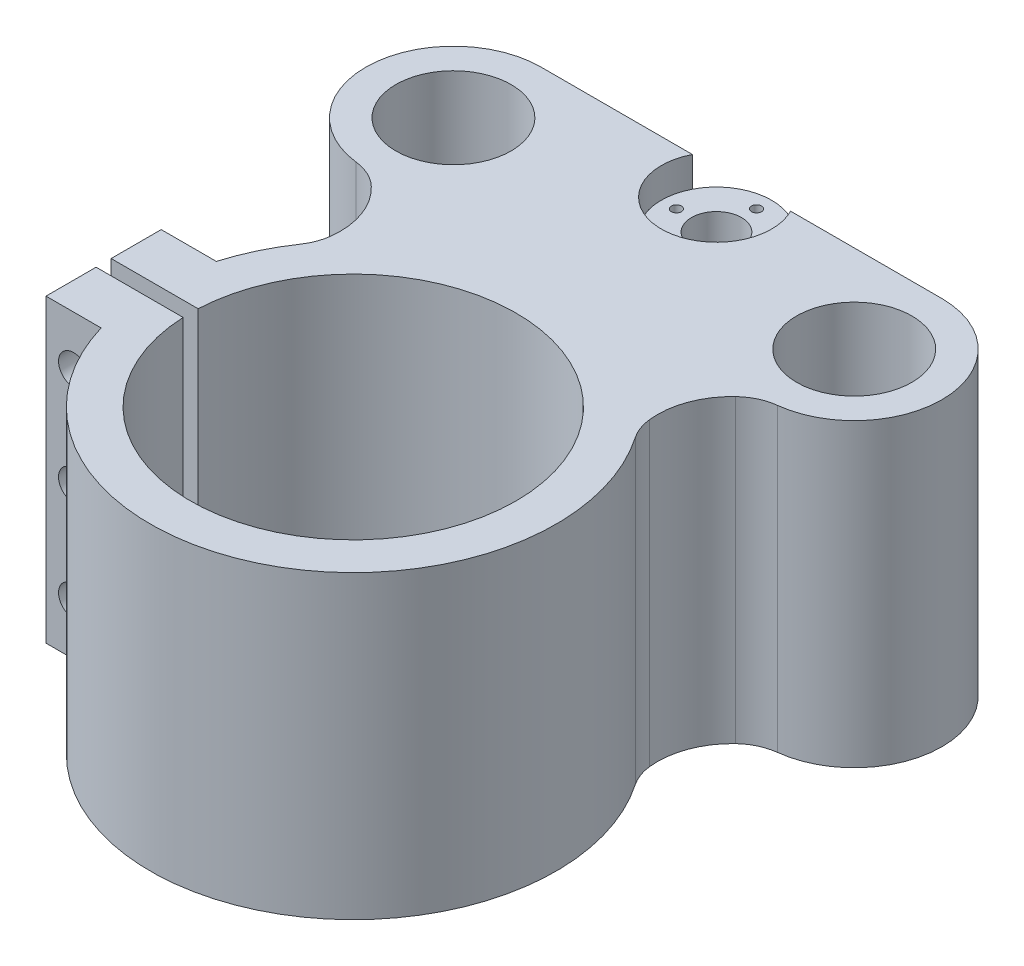
SolidWorks part; units mm, degrees
ref_plane "Front Plane" through (0, 0, 0) normal (0, 0, 1) x (1, 0, 0)
ref_plane "Top Plane" through (0, 0, 0) normal (0, 1, 0) x (1, 0, 0)
ref_plane "Right Plane" through (0, 0, 0) normal (1, 0, 0) x (0, 0, -1)
sketch "Sketch1" plane through (0, 0, 0) normal (0, 1, 0) x (1, 0, 0)
  line L0 (27.0908, 104.5706) -> (107.0908, 104.5706) construction
  line L3 (67.0908, 44.5706) -> (8.9284, 44.5706) construction
  line L5 (67.0908, 44.5706) -> (94.3328, 44.5706) construction
  line L6 (17.2579, 46.0706) -> (34.6255, 46.0706)
  line L7 (17.2579, 56.0706) -> (28.2579, 56.0706)
  line L8 (67.0908, 104.5706) -> (67.0908, 153.14) construction
  line L9 (67.0908, 111.1474) -> (67.0908, 30.162) construction
  line L10 (17.2579, 46.0706) -> (17.2579, 56.0706)
  line L11 (17.2579, 43.0706) -> (34.6255, 43.0706)
  line L12 (17.2579, 43.0706) -> (17.2579, 33.0706)
  line L14 (17.2579, 33.0706) -> (28.2579, 33.0706)
  line L15 (27.0908, 122.0706) -> (107.0908, 122.0706)
  circle A0 centre (27.0908, 104.5706) radius 11.5
  circle A2 centre (27.0908, 104.5706) radius 17.5
  arc A5 (34.6255, 43.0706) -> (34.6255, 46.0706) centre (67.0908, 44.5706) ccw
  arc A6 (28.2579, 33.0706) -> (28.2579, 56.0706) centre (67.0908, 44.5706) ccw
  circle A9 centre (67.0908, 44.5706) radius 32.5 construction
  circle A10 centre (67.0908, 44.5706) radius 40.5 construction
  arc A15 (27.0908, 87.0706) -> (34.6255, 68.7832) centre (20.4303, 73.6304) cw
  arc A16 (107.0908, 87.0706) -> (99.5562, 68.7832) centre (113.7514, 73.6304) ccw
  circle A17 centre (107.0908, 104.5706) radius 11.5
  circle A18 centre (107.0908, 104.5706) radius 17.5
  point P25 (67.0908, 122.0706)
  dimension "D1" = 23
  dimension "D4" = 60
  dimension "D7" = 65
  dimension "D8" = 8
  dimension "D13" = 11
  dimension "D5" = 15
  dimension "D2" = 80
  dimension "D9" = 0
  dimension "D11" = 1.5
  dimension "D12" = 10
  dimension "D3" = 6
extrude "Boss-Extrude1" add sketch "Sketch1" along normal blind 60 contours A6 A5 | A2 A0 | A6 A2 | A2 A6 | A6 | A6 L10 | A6 | A18 A17 region at (18.4712, 0, -51.0706) region at (67.0908, 0, -99.9598) region at (10.0858, 0, -104.5706) region at (90.0858, 0, -104.5706)
sketch "Sketch2" plane through (-1.1118, 0, -33.0706) normal (0, 0, 1) x (1, 0, 0)
  line L0 (30.4702, 30) -> (39.2061, 30) construction
  line L1 (18.3696, 60) -> (29.3696, 60) construction
  line L2 (29.3696, 60) -> (29.3696, 0) construction
  line L3 (23.8696, 39.9087) -> (23.8696, 20.4555) construction
  line L4 (18.3696, 60) -> (18.3696, 0) construction
  line L5 (18.3696, 0) -> (29.3696, 0) construction
  circle A0 centre (23.8696, 30) radius 3
  circle A1 centre (23.8696, 50) radius 3
  circle A2 centre (23.8696, 10) radius 3
  dimension "D1" = 6
  dimension "D2" = 2
  dimension "D3" = 20
extrude "Cut-Extrude1" cut sketch "Sketch2" against normal up to surface (23 mm away) and the other way through all up to face at (22.7579, 30, -56.0706)
sketch "Sketch3" plane through (0, 0, -56.0706) normal (0, 0, -1) x (-1, 0, 0)
  line L0 (-28.2579, 60) -> (-28.2579, 0) construction
  line L1 (-17.2579, 45) -> (-28.2579, 45)
  line L2 (-17.2579, 45) -> (-17.2579, 55)
  line L3 (-17.2579, 55) -> (-28.2579, 55)
  line L4 (-28.2579, 45) -> (-28.2579, 55)
  line L5 (-17.2579, 45) -> (-28.2579, 55) construction
  line L6 (-17.2579, 55) -> (-28.2579, 45) construction
  line L8 (-17.2579, 25) -> (-17.2579, 35)
  line L9 (-17.2579, 25) -> (-28.2579, 25)
  line L10 (-28.2579, 25) -> (-28.2579, 35)
  line L11 (-17.2579, 35) -> (-28.2579, 35)
  line L12 (-17.2579, 5) -> (-17.2579, 15)
  line L13 (-17.2579, 5) -> (-28.2579, 5)
  line L14 (-28.2579, 5) -> (-28.2579, 15)
  line L15 (-17.2579, 15) -> (-28.2579, 15)
  point P0 (-22.7579, 50)
  dimension "D1" = 10
  dimension "D2" = 3
extrude "Cut-Extrude2" [suppressed] cut sketch "Sketch3" against normal blind 5
sketch "Sketch5" plane through (0, 60, 0) normal (0, 1, 0) x (1, 0, 0)
  line L0 (27.0908, 104.5706) -> (107.3528, 104.5706) construction
  circle A0 centre (67.0908, 117.0706) radius 11
  circle A1 centre (67.0908, 117.0706) radius 5
  circle A2 centre (67.0908, 117.0706) radius 8 construction
  circle A3 centre (67.0908, 125.0706) radius 1
  circle A16 centre (75.0908, 117.0706) radius 1
  circle A17 centre (67.0908, 109.0706) radius 1
  circle A18 centre (59.0908, 117.0706) radius 1
  point P16 (67.0908, 103.0286)
  point P19 (69.5908, 109.5706)
  point P20 (71.6118, 102.5496)
  point P21 (69.5908, 114.5706)
  point P22 (67.0908, 117.0706)
  line M38 (107.0908, 122.0706) -> (27.0908, 122.0706)
  dimension "D1" = 10
  dimension "D2" = 2
  dimension "D4" = 16
  dimension "D5" = 22
  dimension "D6" = 12.5
  dimension "D3" = 4
extrude "Boss-Extrude2" add sketch "Sketch5" against normal blind 60 contours A0 A3 | A3 region at (56.402, 60, -117.0706) region at (67.0908, 60, -125.0706)
extrude "Cut-Extrude7" cut sketch "Sketch5<12>" against normal blind 6 contours A1 | A18 | A1 A0 A18 A17 A16 M38 | A0 A3 M38 | A3 | A16 | A17 region at (67.0908, 60, -117.0706) region at (64.5832, 60, -106.6398) region at (71.9898, 60, -122.2755) region at (67.0908, 60, -125.0706) region at (59.0908, 60, -117.0706)
sketch "Sketch5<12>" plane through (0, 60, 0) normal (0, 1, 0) x (1, 0, 0) same geometry as "Sketch5"
extrude "Cut-Extrude8" cut sketch "Sketch5<13>" against normal through all contours A1 region at (67.0908, 60, -117.0706)
sketch "Sketch5<13>" plane through (0, 60, 0) normal (0, 1, 0) x (1, 0, 0) same geometry as "Sketch5"
extrude "Cut-Extrude9" cut sketch "Sketch5<14>" against normal blind 6 from surface contours A3 | A18 | A17 | A16 starting at face at (67.0908, 54, -112.0706)
sketch "Sketch5<14>" plane through (0, 60, 0) normal (0, 1, 0) x (1, 0, 0) same geometry as "Sketch5"
fillet "Fillet1" radius 10 4 edges at (107.0908, 30, -87.0706) (27.0908, 30, -87.0706) (99.5562, 30, -68.7832) (34.6255, 30, -68.7832)
